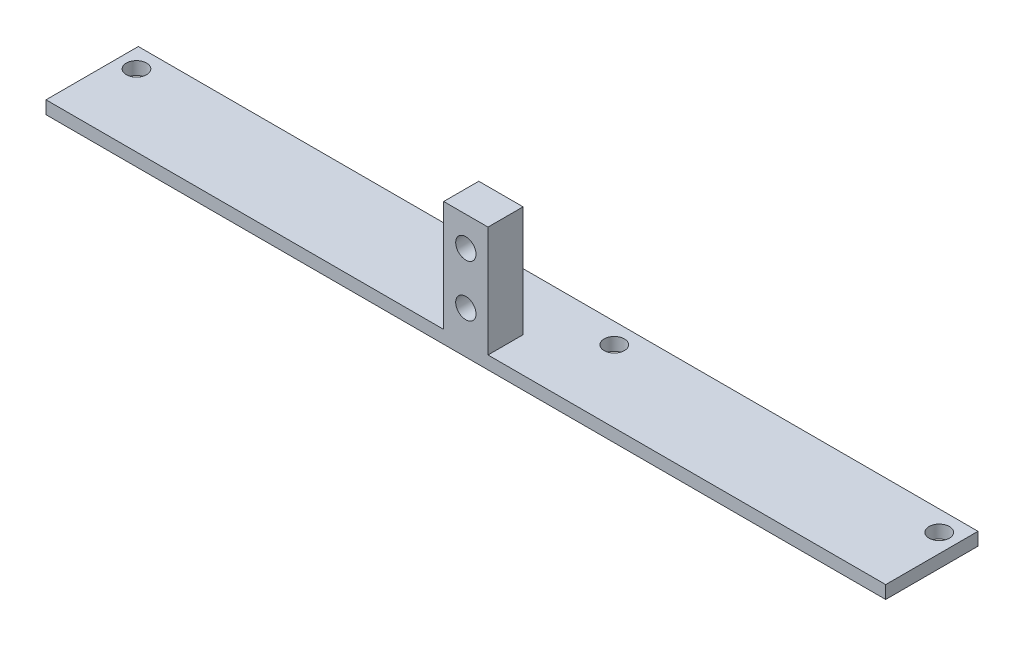
SolidWorks part; units mm, degrees
ref_plane "Front" through (0, 0, 0) normal (0, 0, 1) x (1, 0, 0)
ref_plane "Top" through (0, 0, 0) normal (0, 1, 0) x (1, 0, 0)
ref_plane "Right" through (0, 0, 0) normal (1, 0, 0) x (0, 0, -1)
sketch "Sketch2" plane through (0, 0, 0) normal (0, 1, 0) x (1, 0, 0)
  line L1 (0, 0) -> (114.7, 0)
  line L2 (0, 0) -> (0, 12.5)
  line L3 (0, 12.5) -> (114.7, 12.5)
  line L4 (114.7, 0) -> (114.7, 12.5)
  dimension "D1" = 114.7
  dimension "D2" = 12.5
extrude "bracketBase" add sketch "Sketch2" along normal blind 1.75
sketch "Sketch3" plane through (0, 1.75, 0) normal (0, 1, 0) x (1, 0, 0)
  line L0 (57.35, 12.5) -> (57.35, 0) construction
  line L1 (114.7, 12.5) -> (0, 12.5) construction
  line L2 (0, 0) -> (114.7, 0) construction
  line L3 (0, 12.5) -> (0, 0) construction
  circle A0 centre (3, 9.75) radius 1.375
  circle A1 centre (47, 9.75) radius 1.375
  circle A2 centre (67.7, 9.75) radius 1.375
  circle A3 centre (111.7, 9.75) radius 1.375
  dimension "D1" = 2.75
  dimension "D2" = 2.75
  dimension "D3" = 3
  dimension "D4" = 44
extrude "bottomChassisMountingHoles" cut sketch "Sketch3" against normal blind 1.75
sketch "Sketch4" plane through (0, 0, 0) normal (0, 0, 1) x (1, 0, 0)
  line L0 (57.35, 0) -> (57.35, 26.8195) construction
  line L1 (114.7, 0) -> (120.7, 0)
  line L2 (114.7, 0) -> (114.7, 16.75)
  line L3 (114.7, 16.75) -> (120.7, 16.75)
  line L4 (120.7, 0) -> (120.7, 16.75)
  line L5 (0, 0) -> (114.7, 0) construction
  line L6 (0, 16.75) -> (-6, 16.75)
  line L7 (-6, 0) -> (-6, 16.75)
  line L8 (0, 0) -> (-6, 0)
  line L9 (0, 0) -> (0, 16.75)
  line L11 (54.35, 0) -> (60.35, 0)
  line L12 (54.35, 0) -> (54.35, 16.75)
  line L13 (54.35, 16.75) -> (60.35, 16.75)
  line L14 (60.35, 0) -> (60.35, 16.75)
  point P17 (57.35, 0)
  dimension "D1" = 16.75
  dimension "D2" = 6
extrude "mountingTabs" add sketch "Sketch4" against normal blind 4.75
sketch "Sketch5" plane through (0, 0, -12.5) normal (0, 0, -1) x (-1, 0, 0)
  line L0 (-120.7, 0) -> (-120.7, 16.75) construction
  line L1 (-114.7, 0) -> (-120.7, 0)
  line L2 (-114.7, 0) -> (-114.7, 1.75)
  line L3 (-114.7, 1.75) -> (-120.7, 1.75)
  line L4 (-120.7, 0) -> (-120.7, 1.75)
  line L5 (-114.7, 1.75) -> (0, 1.75) construction
  line L6 (6, 16.75) -> (6, 0) construction
  line L7 (0, 0) -> (6, 0)
  line L8 (0, 0) -> (0, 1.75)
  line L9 (0, 1.75) -> (6, 1.75)
  line L10 (6, 0) -> (6, 1.75)
extrude "extension" add sketch "Sketch5" against normal up to surface (7.75 mm away) up to face at (-2.4, 7.05, -4.75)
sketch "Sketch6" plane through (0, 0, -4.75) normal (0, 0, -1) x (-1, 0, 0)
  line L0 (-57.35, 0) -> (-57.35, 1.75) construction
  line L1 (-120.7, 0) -> (6, 0) construction
  line L2 (-54.35, 1.75) -> (-60.35, 1.75) construction
  line L3 (-60.35, 16.75) -> (-54.35, 16.75) construction
  line L4 (-120.7, 16.75) -> (-114.7, 16.75) construction
  circle A0 centre (-57.35, 12.75) radius 1.375
  circle A1 centre (-57.35, 5.75) radius 1.375
  circle A2 centre (-117.7, 12.75) radius 1.375
  circle A3 centre (-117.7, 5.75) radius 1.375
  circle A4 centre (3, 5.75) radius 1.375
  circle A5 centre (3, 12.75) radius 1.375
  point P12 (-57.35, 16.75)
  point P19 (-117.7, 16.75)
  dimension "D1" = 2.75
  dimension "D2" = 4
  dimension "D3" = 7
extrude "rearShellMountingHoles" cut sketch "Sketch6" against normal blind 4.75
sketch "Sketch8" plane through (0, 1.75, 0) normal (0, 1, 0) x (1, 0, 0)
  line L0 (57.35, 12.5) -> (57.35, 5.75) construction
  line L1 (120.7, 12.5) -> (-6, 12.5) construction
  line L2 (53.35, 5.75) -> (61.35, 5.75) construction
  line L3 (120.7, 4.75) -> (120.7, 12.5) construction
  circle A0 centre (120.95, 8.5675) radius 3.25
  circle A1 centre (-6.25, 8.5675) radius 3.25
  dimension "D1" = 6.5
  dimension "D2" = 3.9325
  dimension "D3" = 0.25
extrude "Cut-Extrude2" cut sketch "Sketch8" against normal blind 10
sketch "Sketch9" plane through (0, 1.75, 0) normal (0, -1, 0) x (1, 0, 0)
  line L0 (120.7, -5.3271) -> (122.423, -5.1942)
  line L1 (122.423, -5.1942) -> (122.9332, -11.8079)
  line L2 (122.9332, -11.8079) -> (120.7, -11.8079)
  arc A0 (120.7, -5.3271) -> (120.7, -11.8079) centre (120.95, -8.5675) ccw construction
  arc A1 (120.7, -5.3271) -> (120.7, -11.8079) centre (120.95, -8.5675) ccw
  circle A2 centre (-6.25, -8.5675) radius 3.25
  arc A3 (-6, -11.8079) -> (-6, -5.3271) centre (-6.25, -8.5675) ccw construction
extrude "Cut-Extrude3" cut sketch "Sketch9" against normal blind 10 rebuild error yes
sketch "Sketch10" plane through (0, 1.75, 0) normal (0, 1, 0) x (1, 0, 0)
  line L0 (57.35, 12.5) -> (57.35, 0) construction
  line L1 (120.7, 12.5) -> (114.2, 12.5)
  line L2 (120.7, 12.5) -> (120.7, 0)
  line L3 (120.7, 0) -> (114.2, 0)
  line L4 (114.2, 12.5) -> (114.2, 0)
  line L5 (120.7, 12.5) -> (-6, 12.5) construction
  line L6 (60.35, 0) -> (54.35, 0) construction
  line L7 (61.35, 0) -> (113.7, 0) construction
  line L8 (-6, 0) -> (0.5, 0)
  line L9 (0.5, 12.5) -> (0.5, 0)
  line L10 (-6, 12.5) -> (0.5, 12.5)
  line L11 (-6, 12.5) -> (-6, 0)
  dimension "D1" = 6.5
extrude "Cut-Extrude4" cut sketch "Sketch10" against normal through all both and the other way through all
